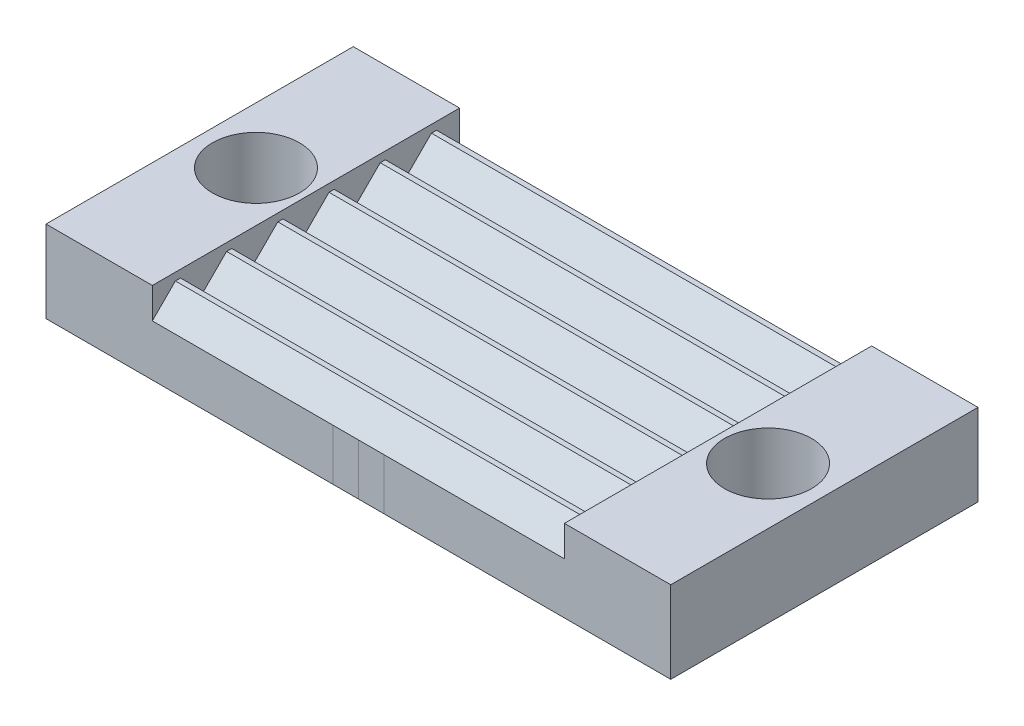
SolidWorks part; units mm, degrees
note: The reader was unsure of these and kept them because the rebuilt part matched: shared geometry of "Sketch1<3>", "Sketch1<4>", "Croquis1<4>", "Croquis1<6>".
ref_plane "Alzado" through (0, 0, 0) normal (0, 0, 1) x (1, 0, 0)
ref_plane "Planta" through (0, 0, 0) normal (0, 1, 0) x (1, 0, 0)
ref_plane "Vista lateral" through (0, 0, 0) normal (1, 0, 0) x (0, 0, -1)
sketch "Croquis1" plane through (0, 0, 0) normal (0, 1, 0) x (1, 0, 0)
  line L0 (0, -16.4018) -> (0, 78.9163) construction
  line L1 (-63.9099, 0) -> (63.9099, 0) construction
  line L2 (-8.0467, 6) -> (8.0467, 6)
  line L3 (8.0467, 6) -> (8.0467, 2.4617)
  line L4 (-8.0467, -6) -> (8.0467, -6)
  line L5 (8.0467, -6) -> (8.0467, -2.4617)
  line L6 (-8.0467, -6) -> (-8.0467, -2.4617)
  line L7 (-8.0467, 6) -> (-8.0467, 2.4617)
  line L8 (8.0467, -2.4617) -> (8.0467, 2.4617)
  line L9 (-8.0467, -2.4617) -> (-8.0467, 2.4617)
  line L11 (8.0467, 6) -> (12.2, 6)
  line L12 (8.0467, 6) -> (8.0467, -6)
  line L13 (8.0467, -6) -> (12.2, -6)
  line L14 (12.2, 6) -> (12.2, -6)
  line L15 (-8.0467, 6) -> (-12.2, 6)
  line L16 (-8.0467, 6) -> (-8.0467, -6)
  line L17 (-8.0467, -6) -> (-12.2, -6)
  line L18 (-12.2, 6) -> (-12.2, -6)
  circle A0 centre (10, 0) radius 1.7
  arc A1 (9.6576, -2.1732) -> (9.6576, 2.1732) centre (10, 0) ccw
  arc A2 (8.0467, 2.4617) -> (9.6576, 2.1732) centre (9.2686, 4.6427) ccw
  arc A3 (8.0467, -2.4617) -> (9.6576, -2.1732) centre (9.2686, -4.6427) cw
  arc A4 (-8.0467, -2.4617) -> (-9.6576, -2.1732) centre (-9.2686, -4.6427) ccw
  arc A5 (-8.0467, 2.4617) -> (-9.6576, 2.1732) centre (-9.2686, 4.6427) cw
  arc A6 (-9.6576, -2.1732) -> (-9.6576, 2.1732) centre (-10, 0) cw
  circle A7 centre (-10, 0) radius 1.7
  point P6 (7.8, 0)
  point P10 (8, 0)
  point P19 (0, 0)
  point P28 (0, -6)
  point P29 (-8, 0)
  point P30 (0, 6)
  dimension "D1" = 7.8
  dimension "D5" = 3.4
  dimension "D6" = 5
  dimension "D3" = 10
  dimension "D2" = 2.2
  dimension "D4" = 6
  dimension "D7" = 1.6366
  dimension "D8" = 2.2
extrude "Saliente-Extruir1" add sketch "Croquis1" along normal blind 2 contours L9 L6 L4 L5 L8 L3 L2 L7 | L8 A3 A1 A2 A0 | A6 A4 L9 A5 A7
ref_plane "Plano1" through (3.25, 0, 0) normal (1, 0, 0) x (0, 0, -1)
sketch "Croquis4" plane through (3.25, 0, 0) normal (1, 0, 0) x (0, 0, -1)
  line L0 (-6, 2) -> (-4, 2)
  line L1 (-6, 2) -> (-5.1, 2.9)
  line L2 (-5, 3) -> (-5, 2) construction
  line L3 (-4, 2) -> (-4.9, 2.9)
  line L4 (-5.1, 2.9) -> (-4.9, 2.9)
  dimension "D1" = 1
  dimension "D2" = 1
  dimension "D3" = 0.9
extrude "Saliente-Extruir2" add sketch "Croquis4" against normal up to surface (16.0934 mm away) from surface at 4.7967 up to face at (-8.0467, 1, -4.2309) starting at face at (8.0467, 1, -4.2309)
pattern_linear "MatrizL1" count 6 spacing 2 along (0, 0, -1) of "Saliente-Extruir2"
sketch "Sketch1" plane through (0, 0, 6) normal (0, 0, 1) x (1, 0, 0)
  line L0 (0, 2) -> (0, 0)
  line L1 (-8.0467, 2) -> (8.0467, 2) construction
  line L4 (-1, 2) -> (1, 2)
  line L5 (-1, 2) -> (-1, 0)
  line L6 (-1, 0) -> (1, 0)
  line L7 (1, 2) -> (1, 0)
  dimension "D1" = 1
  dimension "D2" = 1
extrude "Cut-Extrude1" cut sketch "Sketch1" against normal blind 0.1
extrude "Boss-Extrude1" add sketch "Sketch1<3>" against normal blind 0.1 separate body
sketch "Sketch1<3>" plane through (0, 0, 6) normal (0, 0, 1) x (1, 0, 0) same geometry as "Sketch1"
extrude "Boss-Extrude2" add sketch "Sketch1<4>" against normal blind 0.1 separate body
sketch "Sketch1<4>" plane through (0, 0, 6) normal (0, 0, 1) x (1, 0, 0) same geometry as "Sketch1"
extrude "Boss-Extrude3" add sketch "Croquis1<4>" along normal blind 1.2 from surface at 2 contours A6 A4 L9 A5 A7 | L8 A3 A1 A2 A0 starting at face at (-0.5, 2, 5.95)
sketch "Croquis1<4>" plane through (0, 0, 0) normal (0, 1, 0) x (1, 0, 0) same geometry as "Croquis1"
extrude "Boss-Extrude4" add sketch "Croquis1<6>" along normal up to surface (3.2 mm away) contours A3 L5 L13 L14 A1 | L3 A2 A1 L14 L11 | A4 A6 L18 L17 L6 | L18 A6 A5 L7 L15 up to face at (9.4756, 3.2, 0)
sketch "Croquis1<6>" plane through (0, 0, 0) normal (0, 1, 0) x (1, 0, 0) same geometry as "Croquis1"
